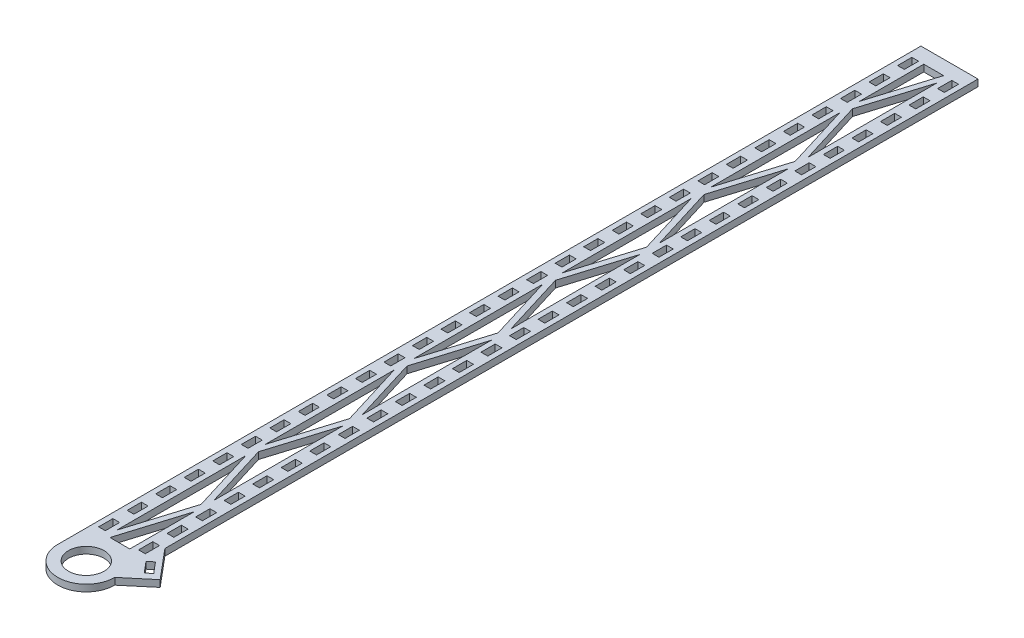
SolidWorks part; units mm, degrees
ref_plane "Front Plane" through (0, 0, 0) normal (0, 0, 1) x (1, 0, 0)
ref_plane "Top Plane" through (0, 0, 0) normal (0, 1, 0) x (1, 0, 0)
ref_plane "Right Plane" through (0, 0, 0) normal (1, 0, 0) x (0, 0, -1)
sketch "Sketch1" plane through (0, 0, 0) normal (0, 1, 0) x (1, 0, 0)
  line L1 (12.7, -192.0875) -> (-12.7, -192.0875)
  line L2 (12.7, -192.0875) -> (12.7, 192.0875)
  line L3 (12.7, 192.0875) -> (-12.7, 192.0875)
  line L4 (-12.7, -192.0875) -> (-12.7, 192.0875)
  line L5 (0, 0) -> (-12.7, 192.0875) construction
  line L6 (12.7, 192.0875) -> (-12.7, -192.0875) construction
  line L9 (12.7, -192.0875) -> (0, 0) construction
  point P0 (0, 0)
  dimension "D1" = 384.175
  dimension "D2" = 25.4
extrude "Boss-Extrude1" add sketch "Sketch1" along normal mid plane 3
sketch "Sketch2" plane through (0, 1.5, 0) normal (0, 1, 0) x (1, 0, 0)
  line L0 (-12.7, -192.0875) -> (12.7, -192.0875) construction
  line L1 (12.7, -192.0875) -> (23.6726, -182.8804)
  line L2 (23.6726, -182.8804) -> (12.7, -169.8038)
  line L3 (12.7, -192.0875) -> (12.7, 192.0875) construction
  line L4 (12.7, -169.8038) -> (12.7, -192.0875)
  circle A0 centre (0, -192.0875) radius 12.7
  line M5 (-12.7, -192.0875) -> (12.7, -192.0875)
  line M6 (12.7, -192.0875) -> (12.7, 192.0875)
  dimension "D1" = 50
  dimension "D2" = 25.4
extrude "Boss-Extrude2" add sketch "Sketch2" against normal up to surface (3 mm away) contours A0 M5 | L1 L2 M6 region at (16.3575, 1.5, 181.5906) region at (0, 1.5, 197.4775) up to face at (0, -1.5, 0)
sketch "Sketch3" plane through (0, 1.5, 0) normal (0, 1, 0) x (1, 0, 0)
  line L0 (-12.7, -192.0875) -> (-12.7, 192.0875) construction
  line L5 (12.7, -192.0875) -> (-12.7, -192.0875) construction
  line L6 (12.7, -192.0875) -> (12.7, 192.0875) construction
  line L7 (23.6726, -182.8804) -> (12.7, -169.8038) construction
  line L8 (12.7, -192.0875) -> (23.6726, -182.8804) construction
  line B0 (-7.39, -176.2125) -> (-10.39, -176.2125)
  line B1 (-7.39, -176.2125) -> (-7.39, -169.8625)
  line B2 (-7.39, -169.8625) -> (-10.39, -169.8625)
  line B3 (-10.39, -176.2125) -> (-10.39, -169.8625)
  line B4 (-7.39, -176.2125) -> (-10.39, -169.8625) construction
  line B5 (-7.39, -169.8625) -> (-10.39, -176.2125) construction
  line B6 (10.39, -176.2125) -> (7.39, -176.2125)
  line B7 (10.39, -176.2125) -> (10.39, -169.8625)
  line B8 (10.39, -169.8625) -> (7.39, -169.8625)
  line B9 (7.39, -176.2125) -> (7.39, -169.8625)
  line B10 (10.39, -176.2125) -> (7.39, -169.8625) construction
  line B11 (10.39, -169.8625) -> (7.39, -176.2125) construction
  line B12 (19.8621, -181.9331) -> (17.564, -183.8614)
  line B13 (19.8621, -181.9331) -> (15.7804, -177.0687)
  line B14 (15.7804, -177.0687) -> (13.4823, -178.9971)
  line B15 (17.564, -183.8614) -> (13.4823, -178.9971)
  line B16 (19.8621, -181.9331) -> (13.4823, -178.9971) construction
  line B17 (15.7804, -177.0687) -> (17.564, -183.8614) construction
  dimension "D1" = 3.81
  dimension "D2" = 19.05
  dimension "D3" = 3.81
  dimension "D4" = 3.81
  dimension "D5" = 6.35
sketch_block_instance "SlotGeometry-1"
sketch_block "SlotGeometry" parameters "D1"=6.35, "D2"=3
sketch_block_instance "SlotGeometry-2"
sketch_block_instance "SlotGeometry-3"
extrude "Slot1" cut sketch "Sketch3" against normal through all both and the other way through all contours B3 B0 B1 B2 region at (-8.89, 1.5, 173.0375)
extrude "Slot2" cut sketch "Sketch3<3>" against normal through all both and the other way through all contours B9 B6 B7 B8 region at (8.89, 1.5, 173.0375)
sketch "Sketch3<3>" plane through (0, 1.5, 0) normal (0, 1, 0) x (1, 0, 0) same geometry as "Sketch3"
extrude "AngleSlot" cut sketch "Sketch3<4>" against normal through all both and the other way through all contours B15 B12 B13 B14 region at (16.6722, 1.5, 180.4651)
sketch "Sketch3<4>" plane through (0, 1.5, 0) normal (0, 1, 0) x (1, 0, 0) same geometry as "Sketch3"
pattern_linear "Slots1" count 34 spacing 12.7 along (0, 0, -1) of "Slot1"
pattern_linear "LPattern2" count 34 spacing 12.7 along (0, 0, -1) of "Slot2"
sketch "Sketch5" plane through (0, 1.5, 0) normal (0, 1, 0) x (1, 0, 0)
  circle A0 centre (0, -192.0875) radius 7.9375
  dimension "D1" = 15.875
extrude "Cut-Extrude4" cut sketch "Sketch5" against normal through all both and the other way through all
sketch "Sketch6" plane through (0, 1.5, 0) normal (0, 1, 0) x (1, 0, 0)
  line L0 (12.7, 192.0875) -> (-12.7, 192.0875) construction
  line L1 (5.08, -177.8) -> (-5.08, -177.8)
  line L2 (5.08, -177.8) -> (5.08, 185.7375)
  line L3 (5.08, 185.7375) -> (-5.08, 185.7375)
  line L4 (-5.08, -177.8) -> (-5.08, 185.7375)
  line L5 (5.08, -177.8) -> (-5.08, 185.7375) construction
  line L6 (5.08, 185.7375) -> (-5.08, -177.8) construction
  line L7 (-5.08, -177.8) -> (5.08, -144.7511) construction
  line L8 (5.08, -144.7511) -> (-5.08, -111.7023) construction
  line L9 (-5.08, -111.7023) -> (5.08, -78.6534) construction
  line L10 (5.08, -78.6534) -> (-5.08, -45.6045) construction
  line L11 (-5.08, -45.6045) -> (5.08, -12.5557) construction
  line L12 (5.08, -12.5557) -> (-5.08, 20.4932) construction
  line L13 (-5.08, 20.4932) -> (5.08, 53.542) construction
  line L14 (5.08, 53.542) -> (-5.08, 86.5909) construction
  line L15 (-5.08, 86.5909) -> (5.08, 119.6398) construction
  line L16 (5.08, 119.6398) -> (-5.08, 152.6886) construction
  line L17 (-5.08, 152.6886) -> (5.08, 185.7375) construction
  line L18 (5.08, -144.7511) -> (-5.08, -144.7511) construction
  line L19 (-3.8661, -178.1732) -> (6.4087, -144.7511)
  line L20 (6.4087, -144.7511) -> (-3.7513, -111.7023)
  line L21 (-3.7513, -111.7023) -> (6.4087, -78.6534)
  line L22 (6.4087, -78.6534) -> (-3.7513, -45.6045)
  line L23 (-3.7513, -45.6045) -> (6.4087, -12.5557)
  line L24 (6.4087, -12.5557) -> (-3.7513, 20.4932)
  line L25 (-3.7513, 20.4932) -> (6.4087, 53.542)
  line L26 (6.4087, 53.542) -> (-3.7513, 86.5909)
  line L27 (-3.7513, 86.5909) -> (6.4087, 119.6398)
  line L28 (6.4087, 119.6398) -> (-3.7513, 152.6886)
  line L29 (-3.7513, 152.6886) -> (6.2939, 185.3643)
  line L30 (-6.2939, -177.4268) -> (3.7513, -144.7511)
  line L31 (3.7513, -144.7511) -> (-6.4087, -111.7023)
  line L32 (-6.4087, -111.7023) -> (3.7513, -78.6534)
  line L33 (3.7513, -78.6534) -> (-6.4087, -45.6045)
  line L34 (-6.4087, -45.6045) -> (3.7513, -12.5557)
  line L35 (3.7513, -12.5557) -> (-6.4087, 20.4932)
  line L36 (-6.4087, 20.4932) -> (3.7513, 53.542)
  line L37 (3.7513, 53.542) -> (-6.4087, 86.5909)
  line L38 (-6.4087, 86.5909) -> (3.7513, 119.6398)
  line L39 (3.7513, 119.6398) -> (-6.4087, 152.6886)
  line L40 (-6.4087, 152.6886) -> (3.8661, 186.1107)
  circle A0 centre (0, -192.0875) radius 7.9375 construction
  point P0 (0, 3.9688)
  dimension "D1" = 10.16
  dimension "D2" = 6.35
  dimension "D3" = 6.35
  dimension "D4" = 1.27
  dimension "D5" = 1.27
extrude "Cut-Extrude5" cut sketch "Sketch6" against normal through all both and the other way through all contours L19 L1 L2 | L30 L31 L4 | L21 L20 L2 | L32 L33 L4 | L23 L22 L2 | L34 L35 L4 | L25 L24 L2 | L36 L37 L4 | L27 L26 L2 | L38 L39 L4 | L29 L28 L2 | L4 L40 L3 region at (2.1362, 1.5, 168.2244) region at (2.1362, 1.5, 111.7023) region at (-2.1362, 1.5, 144.7511) region at (2.1362, 1.5, 45.6045) region at (-2.1362, 1.5, 78.6534) region at (2.1362, 1.5, -20.4932) region at (-2.1362, 1.5, 12.5557) region at (2.1362, 1.5, -86.5909) region at (-2.1362, 1.5, -53.542) region at (2.1362, 1.5, -152.6886) region at (-2.1362, 1.5, -119.6398) region at (-2.1362, 1.5, -176.1619)
